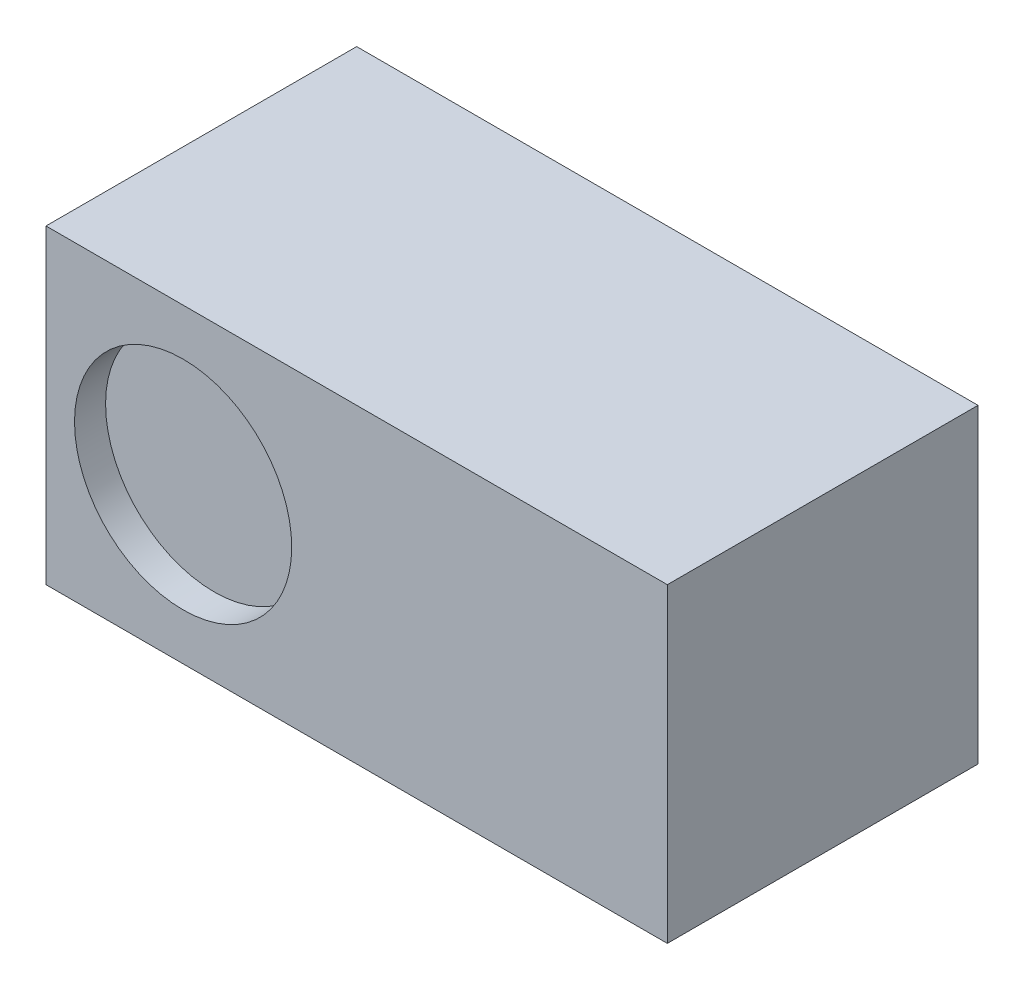
SolidWorks part; units mm, degrees
ref_plane "Front Plane" through (0, 0, 0) normal (0, 0, 1) x (1, 0, 0)
ref_plane "Top Plane" through (0, 0, 0) normal (0, 1, 0) x (1, 0, 0)
ref_plane "Right Plane" through (0, 0, 0) normal (1, 0, 0) x (0, 0, -1)
sketch "Sketch1" plane through (0, 0, 0) normal (0, 0, 1) x (1, 0, 0)
  line L0 (0, 0) -> (0, 8.3017) construction
  line L1 (-25.4, 12.7) -> (25.4, 12.7)
  line L2 (-25.4, 12.7) -> (-25.4, -12.7)
  line L3 (-25.4, -12.7) -> (25.4, -12.7)
  line L4 (25.4, 12.7) -> (25.4, -12.7)
  line L5 (0, 0) -> (11.6554, 0) construction
  dimension "D1" = 25.4
  dimension "D2" = 50.8
extrude "Boss-Extrude1" add sketch "Sketch1" along normal blind 25.4
sketch "Sketch2" plane through (0, 0, 25.4) normal (0, 0, 1) x (1, 0, 0)
  circle A0 centre (-14.1896, 0) radius 8.8792
extrude "Cut-Extrude1" cut sketch "Sketch2" against normal blind 2.54
sketch "Sketch3" plane through (0, 0, 22.86) normal (0, 0, 1) x (1, 0, 0)
  point P0 (-14.1896, 0)
